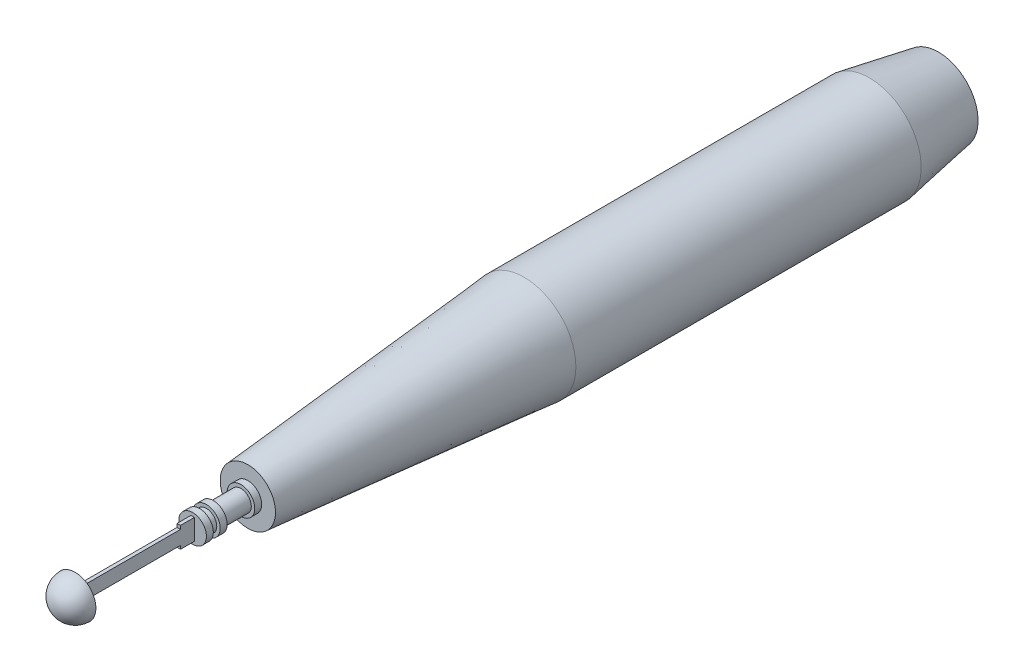
SolidWorks part; units mm, degrees
ref_plane "Front Plane" through (0, 0, 0) normal (0, 0, 1) x (1, 0, 0)
ref_plane "Top Plane" through (0, 0, 0) normal (0, 1, 0) x (1, 0, 0)
ref_plane "Right Plane" through (0, 0, 0) normal (1, 0, 0) x (0, 0, -1)
sketch "Sketch1" plane through (0, 0, 0) normal (0, 0, 1) x (1, 0, 0)
  circle A0 centre (0, 0) radius 7.5
  dimension "D1" = 15
extrude "Boss-Extrude1" add sketch "Sketch1" along normal mid plane 50
sketch "Sketch4" plane through (0, 0, 25) normal (0, 0, 1) x (1, 0, 0)
  circle A0 centre (0, 0) radius 7.5
  dimension "D1" = 15
extrude "Boss-Extrude4" add sketch "Sketch4" along normal blind 40 draft 5
sketch "Sketch5" plane through (0, 0, 65) normal (0, 0, 1) x (1, 0, 0)
  circle A0 centre (0, 0) radius 2
  circle A1 centre (0, 0) radius 1.5
  dimension "D1" = 4
  dimension "D2" = 3
extrude "Boss-Extrude5" add sketch "Sketch5" along normal blind 1 contours A0
extrude "Boss-Extrude6" add sketch "Sketch5<5>" along normal blind 5 contours A1
sketch "Sketch5<5>" plane through (0, 0, 65) normal (0, 0, 1) x (1, 0, 0) same geometry as "Sketch5"
sketch "Sketch6" plane through (0, 0, 70) normal (0, 0, 1) x (1, 0, 0)
  circle A0 centre (0, 0) radius 2
extrude "Boss-Extrude7" add sketch "Sketch6" along normal blind 1
sketch "Sketch8" plane through (0, 0, 71) normal (0, 0, 1) x (1, 0, 0)
  circle A0 centre (0, 0) radius 1.5
  dimension "D1" = 3
extrude "Boss-Extrude8" add sketch "Sketch8" along normal blind 1
sketch "Sketch9" plane through (0, 0, 72) normal (0, 0, 1) x (1, 0, 0)
  circle A0 centre (0, 0) radius 2
  dimension "D1" = 4
extrude "Boss-Extrude9" add sketch "Sketch9" along normal blind 1
sketch "Sketch10" plane through (0, 0, 73) normal (0, 0, 1) x (1, 0, 0)
  line L1 (-0.25, -1.5) -> (0.25, -1.5)
  line L2 (-0.25, -1.5) -> (-0.25, 1.5)
  line L3 (-0.25, 1.5) -> (0.25, 1.5)
  line L4 (0.25, -1.5) -> (0.25, 1.5)
  line L5 (-0.25, -1.5) -> (0.25, 1.5) construction
  line L6 (-0.25, 1.5) -> (0.25, -1.5) construction
  point P0 (0, 0)
  dimension "D1" = 0.5
  dimension "D2" = 3
extrude "Boss-Extrude10" add sketch "Sketch10" along normal blind 2
sketch "Sketch11" plane through (0, 0, 75) normal (0, 0, 1) x (1, 0, 0)
  line L0 (0.25, -1.5) -> (0.25, 1.5) construction
  line L1 (-0.25, -1) -> (0.25, -1)
  line L2 (-0.25, -1) -> (-0.25, 1)
  line L3 (-0.25, 1) -> (0.25, 1)
  line L4 (0.25, -1) -> (0.25, 1)
  line L5 (-0.25, -1) -> (0.25, 1) construction
  line L6 (-0.25, 1) -> (0.25, -1) construction
  point P0 (0, 0)
  dimension "D1" = 2
extrude "Boss-Extrude11" add sketch "Sketch11" along normal blind 15
ref_plane "Plane1" through (0, 0, 0) normal (1, 0, 0) x (0, 0, -1)
sketch "Sketch12" plane through (0, 0, 0) normal (1, 0, 0) x (0, 0, -1)
  line L0 (-90, 0) -> (-93, 0)
  line L1 (-90, -1) -> (-90, 1) construction
  line L2 (-90, 0) -> (-90, 3)
  arc A0 (-90, 3) -> (-93, 0) centre (-90, 0) ccw
  dimension "D2" = 3
  dimension "D1" = 3
revolve "Revolve1" add sketch "Sketch12" angle 360 about L0
sketch "Sketch14" plane through (0, 0, -25) normal (0, 0, -1) x (-1, 0, 0)
  circle A0 centre (0, 0) radius 7.5
extrude "Boss-Extrude13" add sketch "Sketch14" along normal blind 10 draft 10
scale "Scale1" scale about centroid uniform scaling yes scale factor 1.6
sketch "Sketch15" plane through (0, 0, 0) normal (0, 1, 0) x (1, 0, 0)
  line L0 (0, 0) -> (0, -142.886) construction
  point P3 (0, -142.886)
  dimension "D1" = 142.886
